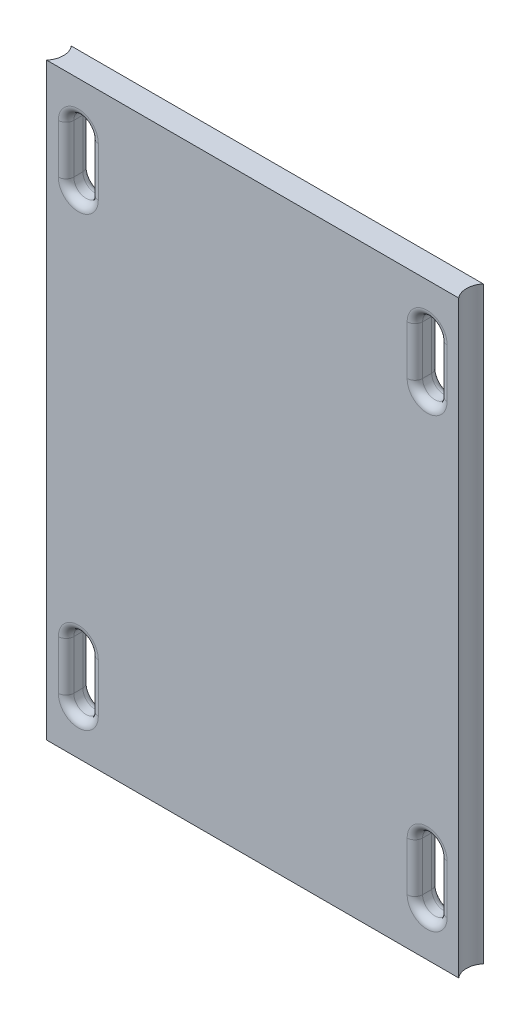
SolidWorks part; units mm, degrees
ref_plane "Front Plane" through (0, 0, 0) normal (0, 0, 1) x (1, 0, 0)
ref_plane "Top Plane" through (0, 0, 0) normal (0, 1, 0) x (1, 0, 0)
ref_plane "Right Plane" through (0, 0, 0) normal (1, 0, 0) x (0, 0, -1)
sketch "Sketch1" plane through (0, 0, 0) normal (0, 1, 0) x (1, 0, 0)
  line L1 (-28.575, -1.5875) -> (28.575, -1.5875)
  line L2 (-28.575, -1.5875) -> (-28.575, 1.5875)
  line L3 (-28.575, 1.5875) -> (28.575, 1.5875)
  line L4 (28.575, -1.5875) -> (28.575, 1.5875)
  line L5 (-28.575, -1.5875) -> (28.575, 1.5875) construction
  line L6 (-28.575, 1.5875) -> (28.575, -1.5875) construction
  circle A0 centre (-28.575, 0) radius 2.4892
  circle A1 centre (28.575, 0) radius 2.4892
  point P0 (0, 0)
  dimension "D2" = 54.6608
  dimension "D3" = 4.9784
  dimension "D1" = 3.175
  dimension "D4" = 57.15
extrude "Boss-Extrude1" add sketch "Sketch1" along normal blind 76.2 contours A1 L3 A0 L1 region at (0, 0, 0)
sketch "Sketch2" plane through (0, 0, 1.5875) normal (0, 0, 1) x (1, 0, 0)
  line L0 (0, 76.2) -> (0, 0) construction
  line L1 (-26.6577, 76.2) -> (26.6577, 76.2) construction
  line L2 (-26.6577, 38.1) -> (26.6577, 38.1) construction
  line L3 (-26.6577, 76.2) -> (-26.6577, 0) construction
  line L4 (26.6577, 76.2) -> (26.6577, 0) construction
  line L5 (-22.5702, 70.2) -> (-22.5702, 63.85) construction
  line L6 (-20.9827, 70.2) -> (-20.9827, 63.85)
  line L7 (-24.1577, 70.2) -> (-24.1577, 63.85)
  line L8 (22.5702, 70.2) -> (22.5702, 63.85) construction
  line L9 (20.9827, 70.2) -> (20.9827, 63.85)
  line L10 (24.1577, 70.2) -> (24.1577, 63.85)
  line L11 (22.5702, 6) -> (22.5702, 12.35) construction
  line L12 (20.9827, 6) -> (20.9827, 12.35)
  line L13 (24.1577, 6) -> (24.1577, 12.35)
  line L14 (-22.5702, 6) -> (-22.5702, 12.35) construction
  line L15 (-20.9827, 6) -> (-20.9827, 12.35)
  line L16 (-24.1577, 6) -> (-24.1577, 12.35)
  arc A0 (-20.9827, 70.2) -> (-24.1577, 70.2) centre (-22.5702, 70.2) ccw
  arc A1 (-24.1577, 63.85) -> (-20.9827, 63.85) centre (-22.5702, 63.85) ccw
  arc A2 (20.9827, 70.2) -> (24.1577, 70.2) centre (22.5702, 70.2) cw
  arc A3 (24.1577, 63.85) -> (20.9827, 63.85) centre (22.5702, 63.85) cw
  arc A4 (20.9827, 6) -> (24.1577, 6) centre (22.5702, 6) ccw
  arc A5 (24.1577, 12.35) -> (20.9827, 12.35) centre (22.5702, 12.35) ccw
  arc A6 (-20.9827, 6) -> (-24.1577, 6) centre (-22.5702, 6) cw
  arc A7 (-24.1577, 12.35) -> (-20.9827, 12.35) centre (-22.5702, 12.35) cw
  point P13 (-22.5702, 67.025)
  point P18 (-22.3471, 67.0776)
  point P21 (22.5702, 67.025)
  point P28 (22.5702, 9.175)
  point P35 (-22.5702, 9.175)
  dimension "D2" = 1.5875
  dimension "D1" = 6.35
  dimension "D3" = 2.5
  dimension "D4" = 6
extrude "Cut-Extrude1" cut sketch "Sketch2" against normal through all both and the other way through all
fillet "Fillet1" radius 1 32 edges at (24.1577, 67.025, 1.5875) (22.5702, 71.7875, 1.5875) (20.9827, 67.025, 1.5875) (20.9827, 67.025, -1.5875) (22.5702, 71.7875, -1.5875) (24.1577, 67.025, -1.5875) (24.1577, 9.175, 1.5875) (22.5702, 13.9375, 1.5875) (20.9827, 9.175, 1.5875) (20.9827, 9.175, -1.5875) (22.5702, 13.9375, -1.5875) (24.1577, 9.175, -1.5875) (-20.9827, 9.175, 1.5875) (-22.5702, 13.9375, 1.5875) (-24.1577, 9.175, 1.5875) (-24.1577, 9.175, -1.5875) (-22.5702, 13.9375, -1.5875) (-20.9827, 9.175, -1.5875) (-20.9827, 67.025, 1.5875) (-22.5702, 71.7875, 1.5875) (-24.1577, 67.025, 1.5875) (-24.1577, 67.025, -1.5875) (-22.5702, 71.7875, -1.5875) (-20.9827, 67.025, -1.5875) (22.5702, 62.2625, 1.5875) (22.5702, 62.2625, -1.5875) (22.5702, 4.4125, 1.5875) (22.5702, 4.4125, -1.5875) (-22.5702, 4.4125, 1.5875) (-22.5702, 4.4125, -1.5875) (-22.5702, 62.2625, 1.5875) (-22.5702, 62.2625, -1.5875)
